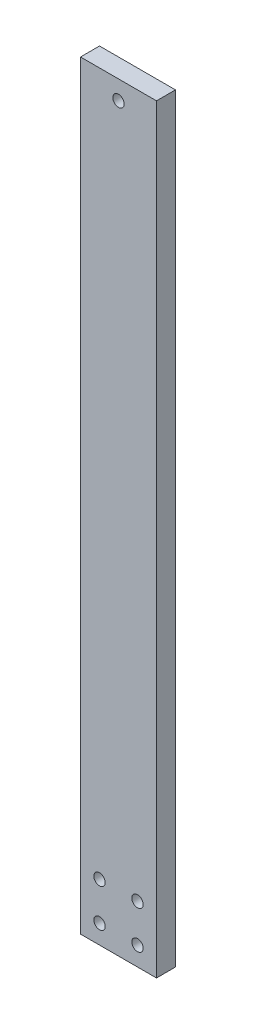
SolidWorks part; units mm, degrees
ref_plane "Front Plane" through (0, 0, 0) normal (0, 0, 1) x (1, 0, 0)
ref_plane "Top Plane" through (0, 0, 0) normal (0, 1, 0) x (1, 0, 0)
ref_plane "Right Plane" through (0, 0, 0) normal (1, 0, 0) x (0, 0, -1)
sketch "Sketch1" plane through (0, 0, 0) normal (0, 0, 1) x (1, 0, 0)
  line L1 (-10, -100) -> (10, -100)
  line L2 (-10, -100) -> (-10, 100)
  line L3 (-10, 100) -> (10, 100)
  line L4 (10, -100) -> (10, 100)
  line L5 (-10, -100) -> (10, 100) construction
  line L6 (-10, 100) -> (10, -100) construction
  point P0 (0, 0)
  dimension "D1" = 20
  dimension "D2" = 200
extrude "Boss-Extrude1" add sketch "Sketch1" along normal blind 5
sketch "Sketch2" plane through (0, 0, 5) normal (0, 0, 1) x (1, 0, 0)
  line L0 (-10, -100) -> (10, -100) construction
  line L1 (-10, 100) -> (-10, -100) construction
  circle A0 centre (-5, -95) radius 1.5
  circle A1 centre (5, -95) radius 1.5
  circle A2 centre (-5, -85) radius 1.5
  circle A3 centre (5, -85) radius 1.5
  point P10 (0, 0)
  dimension "D1" = 3
  dimension "D2" = 3
  dimension "D3" = 3
  dimension "D4" = 3
  dimension "D5" = 10
  dimension "D6" = 10
  dimension "D7" = 10
  dimension "D8" = 5
  dimension "D9" = 5
  dimension "D10" = 10
  dimension "D11" = 5
  dimension "D12" = 10
extrude "Cut-Extrude1" cut sketch "Sketch2" against normal through all
sketch "Sketch3" plane through (0, 0, 5) normal (0, 0, 1) x (1, 0, 0)
  line L0 (10, 100) -> (-10, 100) construction
  line L1 (-10, 100) -> (-10, -100) construction
  circle A0 centre (0, 95) radius 1.5
  dimension "D1" = 3
  dimension "D2" = 5
  dimension "D3" = 10
extrude "Cut-Extrude2" cut sketch "Sketch3" against normal through all
